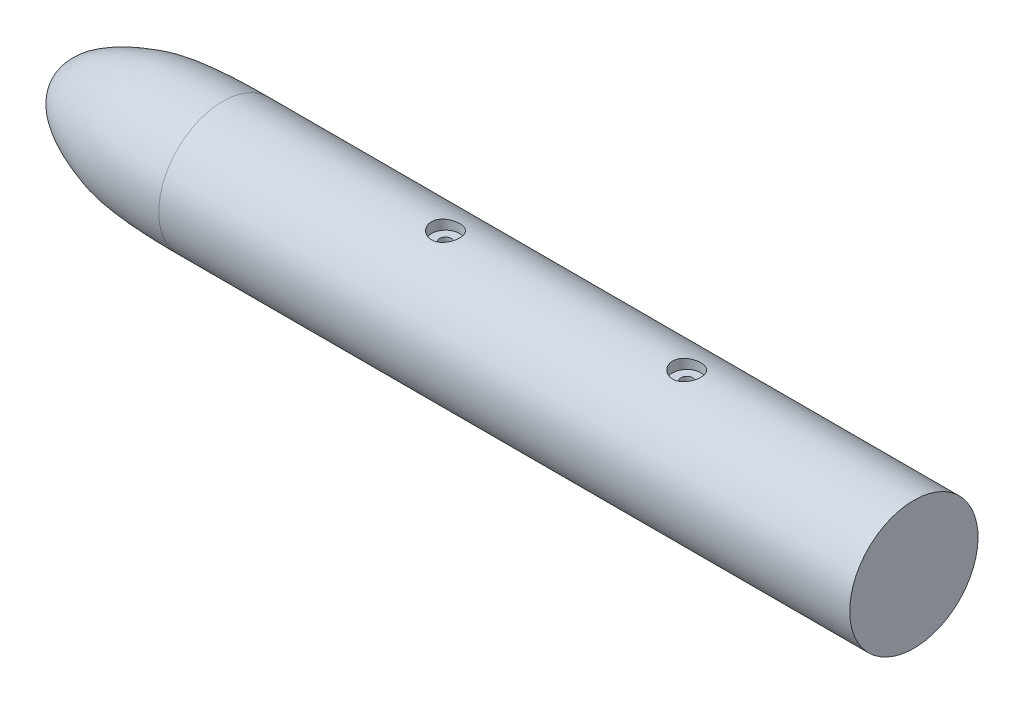
SolidWorks part; units mm, degrees
ref_plane "Ebene vorne" through (0, 0, 0) normal (0, 0, 1) x (1, 0, 0)
ref_plane "Ebene oben" through (0, 0, 0) normal (0, 1, 0) x (1, 0, 0)
ref_plane "Ebene rechts" through (0, 0, 0) normal (1, 0, 0) x (0, 0, -1)
sketch "Skizze4" plane through (0, 0, 0) normal (0, 0, 1) x (1, 0, 0)
  line L0 (40.482, 72.2068) -> (274.0547, 72.2068) construction
  line L1 (258.1087, 24.1447) -> (258.1492, 124.1447) construction
  line L2 (157.9072, 234.6153) -> (727.2405, 234.6153) construction
  line L3 (258.129, 74.1447) -> (25.5481, 74.1447) construction
  line L4 (37.8142, 154.8511) -> (37.8142, -8.7137) construction
  line L5 (164.275, 124.1447) -> (702.8142, 124.1447)
  line L8 (702.8142, 124.1447) -> (702.8142, 74.1447)
  line L9 (702.8142, 74.1447) -> (37.8142, 74.1447)
  spline S0 degree 3 poles (164.275, 124.1447) (136.0956, 124.1447) (107.838, 122.2263) (74.8345, 112.406) (37.8142, 98.4388) (37.8142, 74.1447) knots 0 0 0 0 0.389084 0.472741 1 1 1 1
  dimension "D1" = 100
  dimension "D4" = 50
  dimension "D5" = 665
revolve "Rotation2" add sketch "Skizze4" angle 360 about L9
ref_plane "Ebene1" through (0, 124.1447, 0) normal (0, 1, 0) x (1, 0, 0)
ref_plane "Ebene2" through (0, 62.0724, 0) normal (0, 1, 0) x (1, 0, 0)
ref_plane "Ebene3" through (0, 124.1447, 0) normal (0, 1, 0) x (1, 0, 0)
hole_wizard "Stirnsenkung für M8 Senkschraube (Kopf Button)1" positions "Skizze9" profile "Skizze8" counterbore size "M8" standard "ANSI Metrisch" end condition through all
sketch "Skizze9" plane through (0, 124.1447, 0) normal (0, 1, 0) x (1, 0, 0)
  point P0 (525.8142, 0)
  point P2 (337.8142, 0)
  dimension "D1" = 188
  dimension "D2" = 300
sketch "Skizze8" plane through (525.8142, 124.1447, 0) normal (1, 0, 0) x (0, 0, 1)
  line L0 (0, 0) -> (0, 100)
  line L1 (0, 100) -> (4.5, 100)
  line L3 (4.5, 100) -> (4.5, 8)
  line L4 (4.5, 8) -> (11, 8)
  line L5 (11, 8) -> (11, 0)
  line L7 (11, 0) -> (0, 0)
  line L11 (0, -6.35) -> (0, 107.95) construction
  dimension "Bohrerdurchmesser" = 9
  dimension "Bohrungstiefe" = 100
  dimension "Senkdurchmesser2" = 22
  dimension "Senktiefe2" = 8
ref_plane "Ebene4" through (0, 24.1447, 0) normal (0, -1, 0) x (-1, 0, 0)
hole_wizard "Stirnsenkung für M8 Senkschraube (Kopf Button)2" positions "Skizze11" profile "Skizze10" counterbore size "M8" standard "ANSI Metrisch" end condition through all
sketch "Skizze11" plane through (0, 24.1447, 0) normal (0, -1, 0) x (-1, 0, 0)
  point P0 (-337.8142, 0)
  point P3 (-525.8142, 0)
sketch "Skizze10" plane through (337.8142, 24.1447, 0) normal (1, 0, 0) x (0, 0, -1)
  line L0 (0, 0) -> (0, 100)
  line L1 (0, 100) -> (4.5, 100)
  line L3 (4.5, 100) -> (4.5, 8)
  line L4 (4.5, 8) -> (7.5, 8)
  line L5 (7.5, 8) -> (7.5, 0)
  line L7 (7.5, 0) -> (0, 0)
  line L11 (0, -6.35) -> (0, 107.95) construction
  dimension "Bohrerdurchmesser" = 9
  dimension "Bohrungstiefe" = 100
  dimension "Senkdurchmesser2" = 15
  dimension "Senktiefe2" = 8
